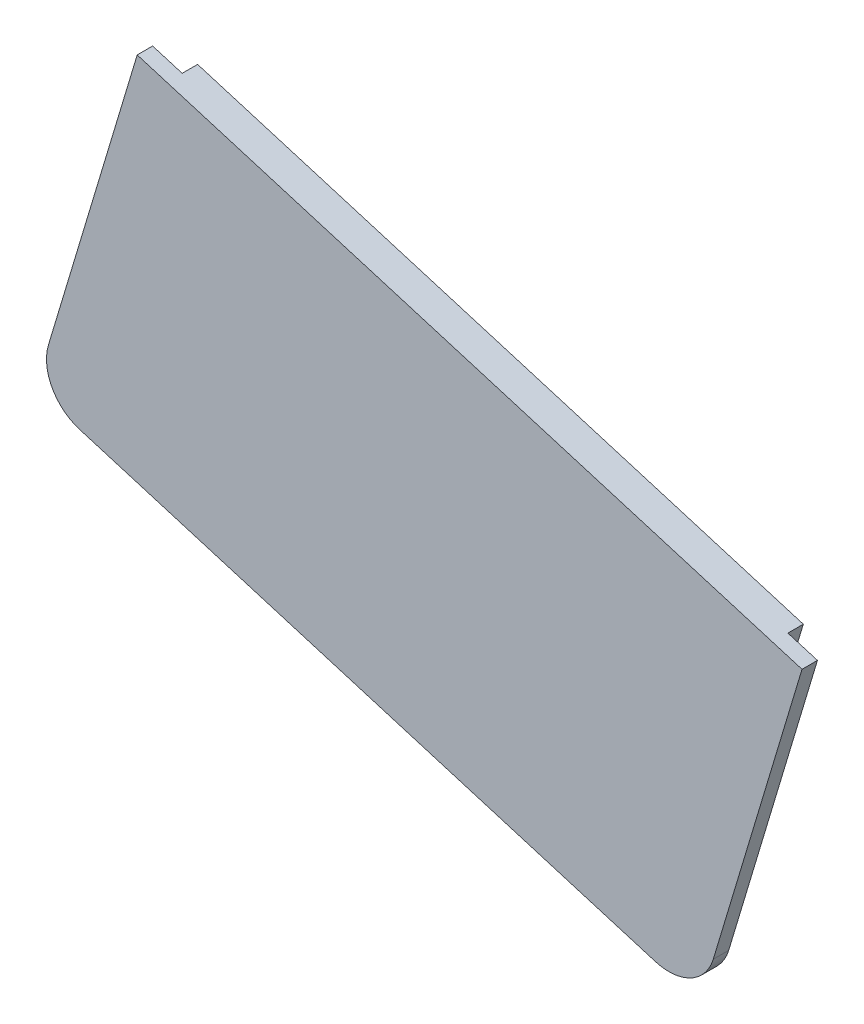
SolidWorks part; units mm, degrees
ref_plane "Front Plane" through (0, 0, 0) normal (0, 0, 1) x (1, 0, 0)
ref_plane "Top Plane" through (0, 0, 0) normal (0, 1, 0) x (1, 0, 0)
ref_plane "Right Plane" through (0, 0, 0) normal (1, 0, 0) x (0, 0, -1)
sketch "Sketch1" plane through (0, 0, 0) normal (0, 0, 1) x (1, 0, 0)
  line L4 (3391.3927, -26.2072) -> (3381.6126, -58.7702)
  line L5 (3383.6229, -62.5063) -> (3420.9745, -73.7247)
  line L6 (3424.7107, -71.7144) -> (3434.4908, -39.1514)
  line L7 (3432.4805, -35.4153) -> (3395.1289, -24.1969)
  line L8 (3391.3927, -26.2072) -> (3381.6126, -58.7702)
  line L9 (3383.6229, -62.5063) -> (3420.9745, -73.7247)
  line L10 (3424.7107, -71.7144) -> (3434.4908, -39.1514)
  line L11 (3432.4805, -35.4153) -> (3395.1289, -24.1969)
  line L16 (3431.9052, -37.3307) -> (3394.5536, -26.1124) construction
  line L17 (3393.3082, -26.7825) -> (3383.5281, -59.3455) construction
  line L18 (3384.1982, -60.5909) -> (3421.5498, -71.8092) construction
  line L19 (3422.7952, -71.1391) -> (3432.5753, -38.5761) construction
  line L20 (3431.9052, -37.3307) -> (3394.5536, -26.1124)
  line L21 (3393.3082, -26.7825) -> (3383.5281, -59.3455)
  line L22 (3384.1982, -60.5909) -> (3421.5498, -71.8092)
  line L23 (3422.7952, -71.1391) -> (3432.5753, -38.5761)
  arc A0 (3383.5281, -59.3455) -> (3384.1982, -60.5909) centre (3384.4858, -59.6331) ccw construction
  arc A4 (3395.1289, -24.1969) -> (3391.3927, -26.2072) centre (3394.2659, -27.0701) ccw
  arc A5 (3381.6126, -58.7702) -> (3383.6229, -62.5063) centre (3384.4858, -59.6331) ccw
  arc A6 (3420.9745, -73.7247) -> (3424.7107, -71.7144) centre (3421.8375, -70.8515) ccw
  arc A7 (3434.4908, -39.1514) -> (3432.4805, -35.4153) centre (3431.6176, -38.2885) ccw
  arc A8 (3395.1289, -24.1969) -> (3391.3927, -26.2072) centre (3394.2659, -27.0701) ccw
  arc A9 (3381.6126, -58.7702) -> (3383.6229, -62.5063) centre (3384.4858, -59.6331) ccw
  arc A10 (3420.9745, -73.7247) -> (3424.7107, -71.7144) centre (3421.8375, -70.8515) ccw
  arc A11 (3434.4908, -39.1514) -> (3432.4805, -35.4153) centre (3431.6176, -38.2885) ccw
  arc A17 (3432.5753, -38.5761) -> (3431.9052, -37.3307) centre (3431.6176, -38.2885) ccw construction
  arc A18 (3394.5536, -26.1124) -> (3393.3082, -26.7825) centre (3394.2659, -27.0701) ccw construction
  arc A19 (3421.5498, -71.8092) -> (3422.7952, -71.1391) centre (3421.8375, -70.8515) ccw construction
  arc A20 (3432.5753, -38.5761) -> (3431.9052, -37.3307) centre (3431.6176, -38.2885) ccw
  arc A21 (3394.5536, -26.1124) -> (3393.3082, -26.7825) centre (3394.2659, -27.0701) ccw
  arc A22 (3383.5281, -59.3455) -> (3384.1982, -60.5909) centre (3384.4858, -59.6331) ccw
  arc A23 (3421.5498, -71.8092) -> (3422.7952, -71.1391) centre (3421.8375, -70.8515) ccw
  dimension "D1" = 0
extrude "Boss-Extrude1" add sketch "Sketch1" against normal blind 1 contours L22 A23 L23 A20 L20 A21 L21 A22 region at (3408.0517, -48.9608, 0)
extrude "Boss-Extrude2" add sketch "Sketch1<4>" along normal blind 1 contours L22 A23 L23 A20 L20 A21 L21 A22 | L10 A11 L11 A8 L8 A9 L9 A10 A23 L22 A22 L21 A21 L20 A20 L23 region at (3393.1894, -25.0694, 0) region at (3408.0517, -48.9608, 0)
sketch "Sketch1<4>" plane through (0, 0, 0) normal (0, 0, 1) x (1, 0, 0) same geometry as "Sketch1"
sketch "Sketch2" plane through (0, 0, -1) normal (0, 0, -1) x (-1, 0, 0)
  line L0 (-3455.7416, -34.9332) -> (-3387.6434, -14.4803)
  line L1 (-3431.9052, -37.3307) -> (-3394.5536, -26.1124) construction
  line L3 (-3455.7416, -34.9332) -> (-3448.7941, -58.0651)
  line L4 (-3387.6434, -14.4803) -> (-3380.6959, -37.6123)
  line L5 (-3448.7941, -58.0651) -> (-3380.6959, -37.6123)
  dimension "D1" = 15
extrude "Cut-Extrude1" cut sketch "Sketch2" against normal blind 10
